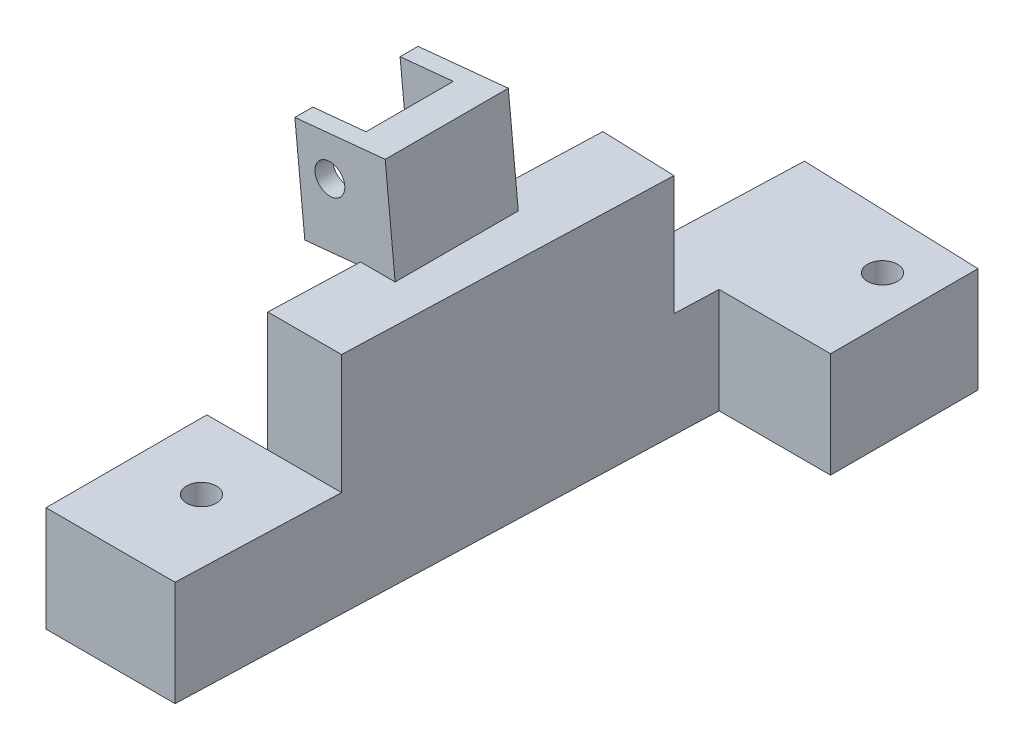
SolidWorks part; units mm, degrees
ref_plane "Front Plane" through (0, 0, 0) normal (0, 0, 1) x (1, 0, 0)
ref_plane "Top Plane" through (0, 0, 0) normal (0, 1, 0) x (1, 0, 0)
ref_plane "Right Plane" through (0, 0, 0) normal (1, 0, 0) x (0, 0, -1)
sketch "Sketch1" plane through (0, 0, 0) normal (0, 0, 1) x (1, 0, 0)
  line L0 (476.9237, 158.5913) -> (479.0335, 137.0791)
  line L1 (479.0335, 137.0791) -> (498.2247, 138.9613)
  line L2 (498.2247, 138.9613) -> (496.115, 160.4735)
  line L3 (496.115, 160.4735) -> (476.9237, 158.5913)
  line L4 (485.2846, 141.5205) -> (469.8952, 140.0112) construction
  line L5 (485.2846, 141.5205) -> (469.8952, 140.0112)
  arc A0 (489.9044, 158.7414) -> (483.4252, 160.4795) centre (484.3549, 151) ccw construction
  arc A1 (491.3026, 144.4842) -> (489.9044, 158.7414) centre (484.3549, 151) ccw construction
  arc A2 (485.2846, 141.5205) -> (491.3026, 144.4842) centre (484.3549, 151) ccw construction
  arc A3 (489.9044, 158.7414) -> (483.4252, 160.4795) centre (484.3549, 151) ccw
  arc A4 (491.3026, 144.4842) -> (489.9044, 158.7414) centre (484.3549, 151) ccw
  arc A5 (485.2846, 141.5205) -> (491.3026, 144.4842) centre (484.3549, 151) ccw
  dimension "D1" = 6.35
  dimension "D2" = 3.81
extrude "Boss-Extrude5" add sketch "Sketch1" against normal blind 22.352 contours A5 L5 L0 L1 L2 L3 A3 A4 region at (482.0029, 140.8922, 0)
sketch "Sketch2" plane through (0, 0, -22.352) normal (0, 0, -1) x (-1, 0, 0)
  line L0 (-488.2317, 159.7003) -> (-476.9237, 158.5913)
  line L1 (-476.9237, 158.5913) -> (-478.6616, 140.8709)
  line L2 (-478.6616, 140.8709) -> (-485.2846, 141.5205)
  arc A0 (-485.2846, 141.5205) -> (-488.2317, 159.7003) centre (-484.3549, 151) cw
  circle A1 centre (-484.3549, 151) radius 3.175 construction
  circle A2 centre (-484.3549, 151) radius 3.175
  circle A3 centre (-484.3549, 151) radius 3.175
  arc M5 (-485.2846, 141.5205) -> (-488.2317, 159.7003) centre (-484.3549, 151) cw
  line M10 (-478.6616, 140.8709) -> (-485.2846, 141.5205)
extrude "Boss-Extrude7" add sketch "Sketch2" against normal blind 3.81 contours L1 L0 A2 M5 M10 region at (482.6025, 158.8937, -22.352)
sketch "Sketch3" plane through (0, 0, 0) normal (0, 0, 1) x (1, 0, 0)
  line L0 (476.9237, 158.5913) -> (479.0335, 137.0791)
  line L1 (479.0335, 137.0791) -> (498.2247, 138.9613)
  line L2 (498.2247, 138.9613) -> (496.115, 160.4735)
  line L3 (496.115, 160.4735) -> (476.9237, 158.5913)
  circle A0 centre (484.3549, 151) radius 3.175 construction
  circle A1 centre (484.3549, 151) radius 3.175
  circle A2 centre (484.3549, 151) radius 3.175
  arc M6 (488.2317, 159.7003) -> (485.2846, 141.5205) centre (484.3549, 151) cw
  line M7 (485.2846, 141.5205) -> (478.6616, 140.8709)
  line M8 (478.6616, 140.8709) -> (479.0335, 137.0791)
  line M9 (479.0335, 137.0791) -> (498.2247, 138.9613)
  line M10 (498.2247, 138.9613) -> (496.115, 160.4735)
  line M11 (496.115, 160.4735) -> (488.2317, 159.7003)
extrude "Boss-Extrude8" add sketch "Sketch3" along normal blind 3.81 contours L3 L0 A1 M6 M7 | M11 M6 M7 M8 M9 M10 region at (482.6025, 158.8937, 0) region at (482.0029, 140.8922, 0)
ref_plane "Plane1" through (0, 138.9613, 0) normal (0, 1, 0) x (1, 0, 0)
sketch "Sketch4" plane through (0, 138.9613, 0) normal (0, 1, 0) x (1, 0, 0)
  line L0 (494.0725, 87.3113) -> (532.2914, 85.9701)
  line L2 (494.0725, 87.3113) -> (490.2062, -22.86)
  line L4 (508.6117, 54.6403) -> (504.6925, -57.0385)
  line L5 (532.2914, 85.9701) -> (532.2914, 54.6403)
  line L6 (532.2914, 54.6403) -> (508.6117, 54.6403)
  line L7 (504.6925, -57.0385) -> (477.2694, -57.0385)
  line L8 (477.2694, -57.0385) -> (477.2694, -22.86)
  line L9 (477.2694, -22.86) -> (490.2062, -22.86)
  dimension "D1" = 90
  dimension "D2" = 111.7476
  dimension "D3" = 180
  dimension "D4" = 110.1713
extrude "Boss-Extrude9" add sketch "Sketch4" against normal up to surface (47.7499 mm away)
sketch "Sketch6" plane through (0, 138.9613, 0) normal (0, 1, 0) x (1, 0, 0)
  circle A0 centre (491.3661, -38.1051) radius 3.175
  circle A1 centre (522.9171, 75.0492) radius 3.175
  dimension "D1" = 6.35
  dimension "D2" = 6.35
extrude "Cut-Extrude1" cut sketch "Sketch6" against normal blind 6.35
sketch "Sketch8" plane through (0, 138.9613, 0) normal (0, 1, 0) x (1, 0, 0)
  circle A0 centre (491.3661, -38.1051) radius 3.175
  circle A1 centre (522.9171, 75.0492) radius 3.175
  dimension "D1" = 6.35
  dimension "D2" = 6.35
extrude "Cut-Extrude2" cut sketch "Sketch8" against normal through all
sketch "Sketch9" plane through (0, 138.9613, 0) normal (0, 1, 0) x (1, 0, 0)
sketch "Sketch10" plane through (0, 138.9613, 0) normal (0, 1, 0) x (1, 0, 0)
  line L0 (477.2694, -22.86) -> (477.2694, -57.0385)
  line L1 (477.2694, -57.0385) -> (504.6925, -57.0385)
  line L2 (504.6925, -57.0385) -> (505.8919, -22.86)
  line L3 (504.6925, -57.0385) -> (508.6117, 54.6403) construction
  line L4 (505.8919, -22.86) -> (477.2694, -22.86)
  line L5 (494.0725, 87.3113) -> (532.2914, 85.9701)
  line L6 (532.2914, 85.9701) -> (532.2914, 54.6403)
  line L13 (494.0725, 87.3113) -> (492.6206, 45.9407)
  line L14 (494.0725, 87.3113) -> (491.7928, 22.352) construction
  line L15 (492.6206, 45.9407) -> (508.2871, 45.3909)
  line L16 (508.2871, 45.3909) -> (508.6117, 54.6403)
  line L17 (508.6117, 54.6403) -> (532.2914, 54.6403)
  circle A0 centre (522.9171, 75.0492) radius 3.175
  circle A1 centre (491.3661, -38.1051) radius 3.175
  dimension "D1" = 6.35
  dimension "D2" = 6.35
  dimension "D3" = 41.3962
extrude "Cut-Extrude5" cut sketch "Sketch10" against normal blind 25.4
